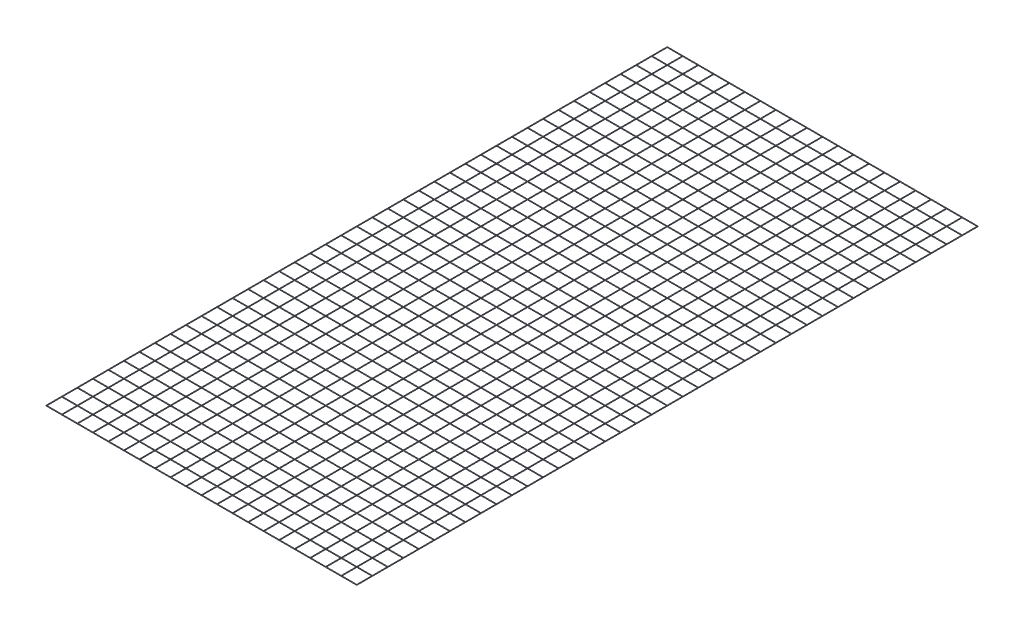
SolidWorks part; units mm, degrees
ref_plane "Piano frontale" through (0, 0, 0) normal (0, 0, 1) x (1, 0, 0)
ref_plane "Piano superiore" through (0, 0, 0) normal (0, 1, 0) x (1, 0, 0)
ref_plane "Piano destro" through (0, 0, 0) normal (1, 0, 0) x (0, 0, -1)
sketch "Schizzo1" plane through (0, 0, 0) normal (0, 0, 1) x (1, 0, 0)
  line L0 (950, 0) -> (1000, 0) construction
  circle A0 centre (0, 0) radius 1
  circle A1 centre (50, 0) radius 1
  circle A2 centre (100, 0) radius 1
  circle A3 centre (150, 0) radius 1
  circle A4 centre (200, 0) radius 1
  circle A5 centre (250, 0) radius 1
  circle A6 centre (300, 0) radius 1
  circle A7 centre (350, 0) radius 1
  circle A8 centre (400, 0) radius 1
  circle A9 centre (450, 0) radius 1
  circle A10 centre (500, 0) radius 1
  circle A11 centre (550, 0) radius 1
  circle A12 centre (600, 0) radius 1
  circle A13 centre (650, 0) radius 1
  circle A14 centre (700, 0) radius 1
  circle A15 centre (750, 0) radius 1
  circle A16 centre (800, 0) radius 1
  circle A17 centre (850, 0) radius 1
  circle A18 centre (900, 0) radius 1
  circle A19 centre (950, 0) radius 1
  circle A20 centre (1000, 0) radius 1
  dimension "D1" = 2
  dimension "D4" = 50
  dimension "D2" = 20
  dimension "D3" = 2
extrude "Estrusione-Estrusione1" add sketch "Schizzo1" along normal blind 2000
sketch "Schizzo2" plane through (0, 0, 0) normal (1, 0, 0) x (0, 0, -1)
  circle A0 centre (0, 0) radius 1
  circle A1 centre (-50, 0) radius 1
  circle A2 centre (-100, 0) radius 1
  circle A3 centre (-150, 0) radius 1
  circle A4 centre (-200, 0) radius 1
  circle A5 centre (-250, 0) radius 1
  circle A6 centre (-300, 0) radius 1
  circle A7 centre (-350, 0) radius 1
  circle A8 centre (-400, 0) radius 1
  circle A9 centre (-450, 0) radius 1
  circle A10 centre (-500, 0) radius 1
  circle A11 centre (-550, 0) radius 1
  circle A12 centre (-600, 0) radius 1
  circle A13 centre (-650, 0) radius 1
  circle A14 centre (-700, 0) radius 1
  circle A15 centre (-750, 0) radius 1
  circle A16 centre (-800, 0) radius 1
  circle A17 centre (-850, 0) radius 1
  circle A18 centre (-900, 0) radius 1
  circle A19 centre (-950, 0) radius 1
  circle A20 centre (-1000, 0) radius 1
  circle A21 centre (-1050, 0) radius 1
  circle A22 centre (-1100, 0) radius 1
  circle A23 centre (-1150, 0) radius 1
  circle A24 centre (-1200, 0) radius 1
  circle A25 centre (-1250, 0) radius 1
  circle A26 centre (-1300, 0) radius 1
  circle A27 centre (-1350, 0) radius 1
  circle A28 centre (-1400, 0) radius 1
  circle A29 centre (-1450, 0) radius 1
  circle A30 centre (-1500, 0) radius 1
  circle A31 centre (-1550, 0) radius 1
  circle A32 centre (-1600, 0) radius 1
  circle A33 centre (-1650, 0) radius 1
  circle A34 centre (-1700, 0) radius 1
  circle A35 centre (-1750, 0) radius 1
  circle A36 centre (-1800, 0) radius 1
  circle A37 centre (-1850, 0) radius 1
  circle A38 centre (-1900, 0) radius 1
  circle A39 centre (-1950, 0) radius 1
  circle A40 centre (-2000, 0) radius 1
  dimension "D1" = 2
  dimension "D2" = 41
extrude "Estrusione-Estrusione2" add sketch "Schizzo2" along normal blind 1000
